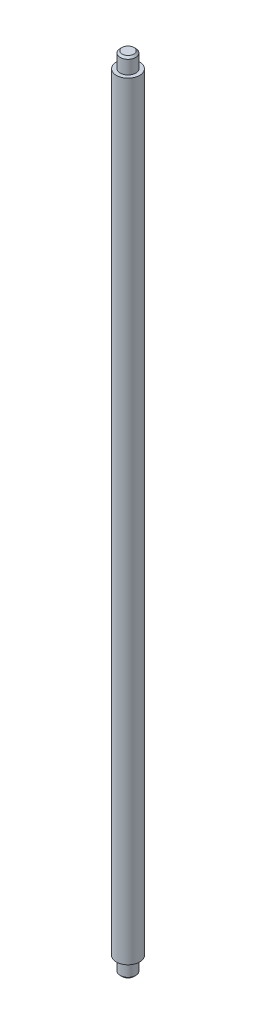
SolidWorks part; units mm, degrees
material "Stainless Steel (ferritic)"
ref_plane "Ön Düzlem" through (0, 0, 0) normal (0, 0, 1) x (1, 0, 0)
ref_plane "Üst Düzlem" through (0, 0, 0) normal (0, 1, 0) x (1, 0, 0)
ref_plane "Sağ Düzlem" through (0, 0, 0) normal (1, 0, 0) x (0, 0, -1)
sketch "Çizim1" plane through (0, 0, 0) normal (0, 1, 0) x (1, 0, 0)
  circle A2 centre (0, 0) radius 3
extrude "Yükseklik-Ekstrüzyon6" add sketch "Çizim1" along normal mid plane 198 contours A2
sketch "Çizim2" plane through (0, 99, 0) normal (0, 1, 0) x (1, 0, 0)
  circle A0 centre (0, 0) radius 2
extrude "Yükseklik-Ekstrüzyon7" add sketch "Çizim2" along normal blind 4
fillet "Radyus1" radius 0.5 1 edges at (0, 103, 2) conic radius 10
sketch "Çizim5" plane through (0, -99, 0) normal (0, -1, 0) x (1, 0, 0)
  circle A0 centre (0, 0) radius 2
extrude "Yükseklik-Ekstrüzyon8" add sketch "Çizim5" along normal blind 4
fillet "Radyus2" radius 0.5 1 edges at (0, -103, -2) conic radius 10
